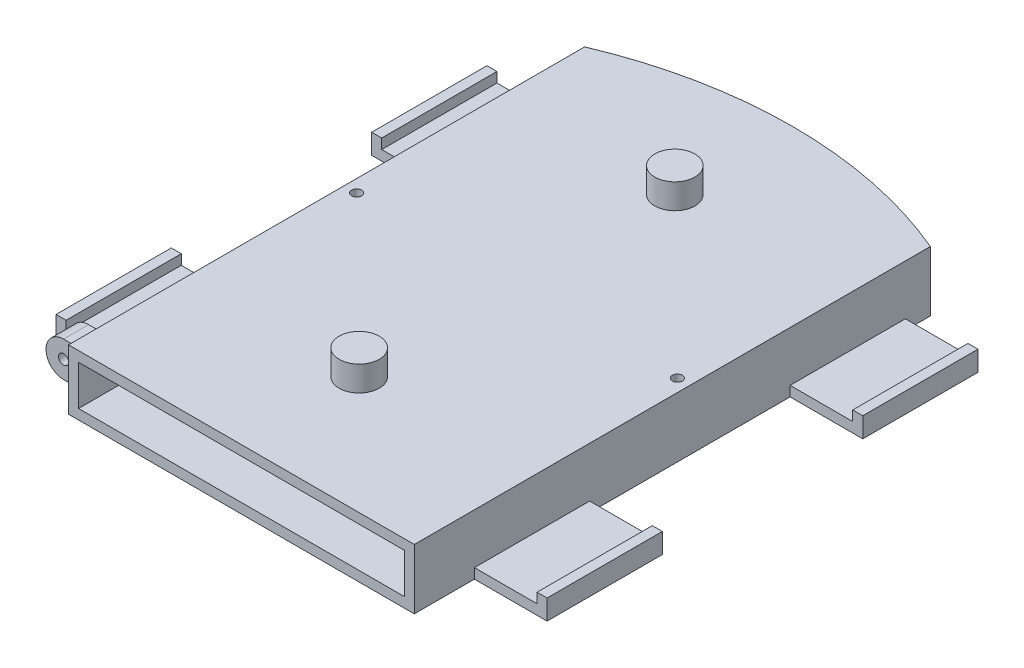
SolidWorks part; units mm, degrees
ref_plane "Alzado" through (0, 0, 0) normal (0, 0, 1) x (1, 0, 0)
ref_plane "Planta" through (0, 0, 0) normal (0, 1, 0) x (1, 0, 0)
ref_plane "Vista lateral" through (0, 0, 0) normal (1, 0, 0) x (0, 0, -1)
sketch "Croquis1" plane through (0, 0, 0) normal (0, 1, 0) x (1, 0, 0)
  line L0 (-31.5, 48.5) -> (31.5, -48.5) construction
  line L1 (-31.5, 48.5) -> (31.5, 48.5)
  line L2 (-31.5, 48.5) -> (-31.5, -48.5)
  line L3 (-31.5, -48.5) -> (31.5, -48.5)
  line L4 (31.5, 48.5) -> (31.5, -48.5)
  line L5 (-32.5, 49.5) -> (32.5, 49.5)
  line L6 (32.5, 49.5) -> (32.5, -49.5)
  line L7 (-32.5, -49.5) -> (32.5, -49.5)
  line L8 (-32.5, 49.5) -> (-32.5, -49.5)
  line L9 (-34.5, 51.5) -> (34.5, 51.5)
  line L10 (34.5, 51.5) -> (34.5, -51.5)
  line L11 (-34.5, -51.5) -> (34.5, -51.5)
  line L12 (-34.5, 51.5) -> (-34.5, -51.5)
  line L13 (-34.5, 51.5) -> (-34.5, 58.5)
  line L14 (-34.5, 58.5) -> (34.5, 58.5)
  line L15 (34.5, 58.5) -> (34.5, 51.5)
  line L16 (-32.5, -49.5) -> (-32.5, -51.5)
  line L17 (32.5, -49.5) -> (32.5, -51.5)
  point P4 (0, 0)
  dimension "D1" = 97
  dimension "D2" = 63
  dimension "D5" = 110
  dimension "D3" = 1
  dimension "D4" = 3
extrude "Saliente-Extruir1" add sketch "Croquis1" against normal blind 2 contours L0 L2 L3 | L1 L0 L4 | L9 L12 L11 L10 L8 L5 L6 L7 | L5 L8 L7 L6 L1 L4 L3 L2 | L17 L7 L16 L11 | L15 L14 L13 L9 region at (10.5, 0, -16.1667) region at (-10.5, 0, 16.1667) region at (-33.7398, 0, 0) region at (0, 0, -49.3816) region at (0, 0, 50.5) region at (0, 0, -55)
extrude "Saliente-Extruir2" add sketch "Croquis1<3>" along normal blind 8 contours L6 L17 L11 L10 L9 L12 L16 L8 L5 region at (-33.7398, 0, 0)
sketch "Croquis1<3>" plane through (0, 0, 0) normal (0, 1, 0) x (1, 0, 0) same geometry as "Croquis1"
sketch "Croquis3" plane through (0, -2, 0) normal (0, -1, 0) x (1, 0, 0)
  line L4 (34.5, 51.5) -> (-34.5, 51.5)
  line L5 (-34.5, 51.5) -> (-34.5, -58.5)
  line L6 (-34.5, -58.5) -> (34.5, -58.5)
  line L7 (34.5, -58.5) -> (34.5, 51.5)
  line L8 (34.5, 51.5) -> (-34.5, 51.5)
  line L9 (-34.5, 51.5) -> (-34.5, -58.5)
  line L11 (34.5, -58.5) -> (34.5, 51.5)
  line L12 (-34.5, -58.5) -> (34.5, -58.5)
  dimension "D1" = 0
extrude "Saliente-Extruir3" add sketch "Croquis3" against normal blind 2 from surface starting at face at (0, 8, 0.5)
sketch "Croquis5" plane through (0, -2, 0) normal (0, -1, 0) x (1, 0, 0)
  line L0 (34.5, 39.5) -> (47, 39.5)
  line L1 (34.5, -58.5) -> (34.5, 51.5) construction
  line L2 (47, 39.5) -> (47, 16.5)
  line L3 (47, 16.5) -> (34.5, 16.5)
  line L4 (34.5, 16.5) -> (34.5, 39.5)
  line L5 (47, 39.5) -> (49, 39.5)
  line L6 (49, 39.5) -> (49, 16.5)
  line L7 (49, 16.5) -> (47, 16.5)
  line L8 (-34.5, 51.5) -> (34.5, 51.5) construction
  line L9 (-34.5, -3.5) -> (34.5, -3.5) construction
  line L10 (-34.5, -58.5) -> (-34.5, 51.5) construction
  line L11 (0, -58.5) -> (0, 51.5) construction
  line L12 (-34.5, -58.5) -> (34.5, -58.5) construction
  line L13 (49, -23.5) -> (47, -23.5)
  line L14 (49, -46.5) -> (49, -23.5)
  line L15 (47, -46.5) -> (49, -46.5)
  line L16 (34.5, -23.5) -> (34.5, -46.5)
  line L17 (47, -23.5) -> (34.5, -23.5)
  line L18 (47, -46.5) -> (47, -23.5)
  line L19 (34.5, -46.5) -> (47, -46.5)
  line L20 (-34.5, -46.5) -> (-47, -46.5)
  line L21 (-47, -46.5) -> (-47, -23.5)
  line L22 (-47, -23.5) -> (-34.5, -23.5)
  line L23 (-34.5, -23.5) -> (-34.5, -46.5)
  line L24 (-47, -46.5) -> (-49, -46.5)
  line L25 (-49, -46.5) -> (-49, -23.5)
  line L26 (-49, -23.5) -> (-47, -23.5)
  line L27 (-49, 16.5) -> (-47, 16.5)
  line L28 (-49, 39.5) -> (-49, 16.5)
  line L29 (-47, 39.5) -> (-49, 39.5)
  line L30 (-34.5, 16.5) -> (-34.5, 39.5)
  line L31 (-47, 16.5) -> (-34.5, 16.5)
  line L32 (-47, 39.5) -> (-47, 16.5)
  line L33 (-34.5, 39.5) -> (-47, 39.5)
  line M9 (-34.5, 51.5) -> (-34.5, -58.5)
  line M11 (34.5, -58.5) -> (34.5, 51.5)
  dimension "D1" = 12.5
  dimension "D2" = 23
  dimension "D3" = 2
  dimension "D4" = 12
extrude "Saliente-Extruir4" add sketch "Croquis5" against normal blind 2 contours L33 L32 L31 M9 | L3 L2 L0 M11 | L19 L18 L17 M11 | L22 L21 L20 M9 region at (40.75, -2, -35) region at (40.75, -2, 28) region at (-40.75, -2, 28) region at (-40.75, -2, -35)
extrude "Saliente-Extruir5" add sketch "Croquis5<3>" against normal blind 4 contours L7 L6 L5 L2 | L18 L15 L14 L13 | L26 L25 L24 L21 | L32 L29 L28 L27 region at (48, -2, 28) region at (48, -2, -35) region at (-48, -2, -35) region at (-48, -2, 28)
sketch "Croquis5<3>" plane through (0, -2, 0) normal (0, -1, 0) x (1, 0, 0) same geometry as "Croquis5"
sketch "Croquis6" plane through (0, 10, 0) normal (0, 1, 0) x (1, 0, 0)
  line L0 (34.5, -51.5) -> (34.5, 58.5) construction
  line L1 (47, -16.5) -> (34.5, -16.5) construction
  line L2 (34.5, -16.5) -> (34.5, 23.5) construction
  line L3 (34.5, -16.5) -> (34.5, -39.5) construction
  line L4 (0, 0) -> (0, -50000) construction
  circle A0 centre (32, 3.5) radius 1
  circle A1 centre (-32, 3.5) radius 1
  point P11 (34.5, 3.5)
  dimension "D1" = 2
  dimension "D2" = 2.5
extrude "Cortar-Extruir1" cut sketch "Croquis6" against normal up to surface (2 mm away) and the other way through all up to face at (0, 8, 1)
sketch "Croquis7" plane through (0, 10, 0) normal (0, 1, 0) x (1, 0, 0)
  line L1 (34.5, -16.5) -> (34.5, -39.5) construction
  line L2 (34.5, 46.5) -> (34.5, 23.5) construction
  circle A0 centre (0, 35) radius 4
  circle A1 centre (0, -28) radius 4
  point P10 (34.5, -28)
  point P11 (34.5, 35)
  dimension "D1" = 8
extrude "Saliente-Extruir6" add sketch "Croquis7" along normal blind 5
sketch "Croquis8" plane through (0, 0, 0) normal (0, 1, 0) x (1, 0, 0)
  line L0 (-34.5, 58.5) -> (0, 58.5) construction
  line L1 (34.5, 58.5) -> (-34.5, 58.5) construction
  line L2 (-34.5, 58.5) -> (-34.5, 51.5) construction
  line L3 (-34.5, 51.5) -> (-34.5, 58.5)
  line L5 (34.5, 51.5) -> (34.5, 58.5) construction
  line L6 (-34.5, 58.5) -> (34.5, 58.5)
  line L7 (34.5, 58.5) -> (34.5, 51.5)
  arc A1 (-34.5, 51.5) -> (34.5, 51.5) centre (0, -30.0179) cw
  point P9 (0, 58.5)
  line M2 (-34.5, 58.5) -> (-34.5, 51.5)
  line M4 (34.5, 51.5) -> (34.5, 58.5)
  line M5 (34.5, 58.5) -> (-34.5, 58.5)
extrude "Cortar-Extruir2" cut sketch "Croquis8" against normal through all both and the other way through all contours A1 L6 M2 | A1 M5 M4 region at (25.9447, 0, -56.415) region at (-25.9447, 0, -56.415)
sketch "Croquis9" plane through (0, 0, 0) normal (0, 1, 0) x (1, 0, 0)
  line L1 (-34.5, 51.5) -> (34.5, 51.5)
  line L2 (-34.5, 51.5) -> (34.5, 51.5)
  arc A1 (34.5, 51.5) -> (-34.5, 51.5) centre (0, -30.0179) ccw
  arc A2 (34.5, 51.5) -> (-34.5, 51.5) centre (0, -30.0179) ccw
  dimension "D1" = 0
extrude "Saliente-Extruir7" add sketch "Croquis9" along normal up to next
sketch "Croquis10" plane through (0, 0, 51.5) normal (0, 0, 1) x (1, 0, 0)
  line L0 (-34.5, 0.5) -> (-38.5, 0.5)
  line L1 (-34.5, -2) -> (-34.5, 10) construction
  line L2 (-34.5, 7.5) -> (-38.5, 7.5)
  line L3 (-34.5, 0.5) -> (-34.5, 7.5)
  line L4 (-32.5, 8) -> (-32.5, 0) construction
  arc A0 (-38.5, 7.5) -> (-38.5, 0.5) centre (-38.5, 4) ccw
  circle A1 centre (-38.5, 4) radius 1
  point P7 (-34.5, 4)
  point P10 (-32.5, 4)
  line M8 (-34.5, 10) -> (-34.5, -2)
  dimension "D2" = 2
  dimension "D3" = 4
  dimension "D1" = 7
extrude "Saliente-Extruir8" add sketch "Croquis10" against normal blind 5 from offset 3 contours L2 A0 L0 A1 M8 | A1 | A1 | L3 L2 A0 L0 region at (-36.5, 0.6026, 51.5) region at (-38.5, 4, 51.5) offset against normal yes
extrude "Cortar-Extruir3" cut sketch "Croquis10<3>" against normal blind 4 from surface contours A1 region at (-38.5, 4, 51.5) starting at face at (-37.375, 4, 48.5)
sketch "Croquis10<3>" plane through (0, 0, 51.5) normal (0, 0, 1) x (1, 0, 0) same geometry as "Croquis10"
